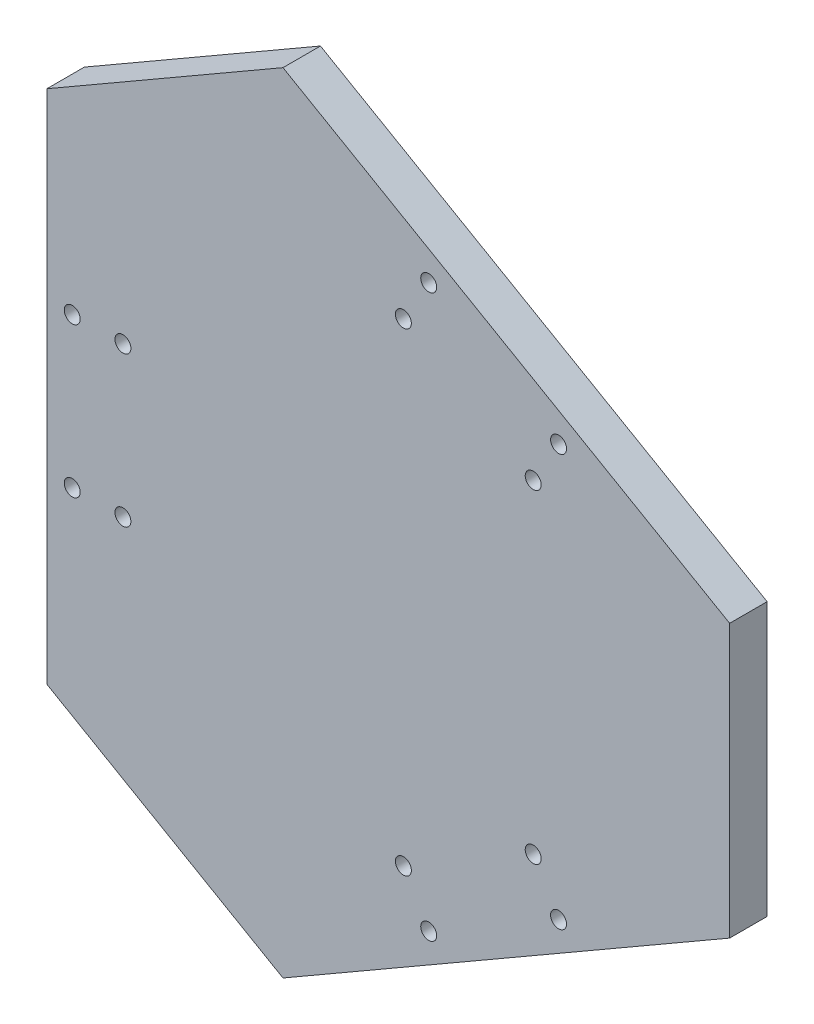
SolidWorks part; units mm, degrees
material "1060 Alloy"
ref_plane "Front Plane" through (0, 0, 0) normal (1, 0, 0) x (0, 1, 0)
ref_plane "Top Plane" through (0, 0, 0) normal (0, 0, 1) x (0, 1, 0)
ref_plane "Right Plane" through (0, 0, 0) normal (0, 1, 0) x (-1, 0, 0)
sketch "Sketch1" plane through (0, 0, 0) normal (0, 0, 1) x (0, 1, 0)
  line L0 (0, 0) -> (-127.8293, 0) construction
  line L4 (0, -207.5586) -> (179.751, 103.7793) construction
  line L5 (150, 86.6025) -> (-150, 86.6025) construction
  line L6 (-150, 86.6025) -> (0, -173.2051) construction
  line L7 (0, -173.2051) -> (150, 86.6025) construction
  line L8 (179.751, 103.7793) -> (-179.751, 103.7793) construction
  line L9 (-179.751, 103.7793) -> (0, -207.5586) construction
  line L10 (-133.563, 23.7793) -> (-87.375, 103.7793)
  line L11 (0, 0) -> (0, 103.7793) construction
  line L12 (-25.4, 86.6025) -> (-25.4, 103.7793) construction
  line L13 (87.375, 103.7793) -> (133.563, 23.7793)
  line L14 (46.188, -127.5586) -> (-46.188, -127.5586)
  line L15 (-46.188, -127.5586) -> (-133.563, 23.7793)
  line L16 (46.188, -127.5586) -> (133.563, 23.7793)
  line L17 (87.375, 103.7793) -> (-87.375, 103.7793)
  circle A0 centre (0, 0) radius 86.6025 construction
  point P17 (-25.4, 95.1909)
  point P18 (-25.4, 78.0142)
  point P19 (25.4, 95.1909)
  point P20 (25.4, 78.0142)
  point P26 (95.1378, -25.5984)
  point P27 (80.2622, -17.01)
  point P28 (69.7378, -69.5925)
  point P29 (54.8622, -61.0041)
  point P32 (-69.7378, -69.5925)
  point P33 (-54.8622, -61.0041)
  point P34 (-95.1378, -25.5984)
  point P35 (-80.2622, -17.01)
  dimension "D1" = 300
  dimension "D3" = 80
  dimension "D4" = 25.4
  dimension "D2" = 17.1767
  dimension "D5" = 3
extrude "Boss-Extrude1" add sketch "Sketch1" against normal mid plane 12.7
hole_wizard "Tap Drill for 1/4-28 Tap1" positions "Sketch2" profile "Sketch3" hole size "1/4-28" standard "ANSI Inch"
sketch "Sketch2" plane through (0, 0, 6.35) normal (0, 0, 1) x (1, 0, 0)
  point P0 (17.01, -80.2622)
  point P3 (25.5984, -95.1378)
  point P6 (69.5925, -69.7378)
  point P9 (61.0041, -54.8622)
  point P12 (61.0041, 54.8622)
  point P15 (69.5925, 69.7378)
  point P18 (25.5984, 95.1378)
  point P21 (17.01, 80.2622)
  point P24 (-78.0142, 25.4)
  point P27 (-95.1909, 25.4)
  point P30 (-95.1909, -25.4)
  point P33 (-78.0142, -25.4)
sketch "Sketch3" plane through (17.01, -80.2622, 6.35) normal (1, 0, 0) x (0, -1, 0)
  line L0 (0, 0) -> (0, 14.3254)
  line L1 (0, 14.3254) -> (2.7051, 12.7)
  line L2 (2.7051, 12.7) -> (2.7051, 0)
  line L5 (2.7051, 0) -> (0, 0)
  line L10 (0, 14.3254) -> (-2.7051, 12.7) construction
  line L11 (0, -6.35) -> (0, 107.95) construction
  dimension "Hole Dia." = 5.4102
  dimension "Hole Depth" = 12.7
  dimension "Drill Angle" = 118
